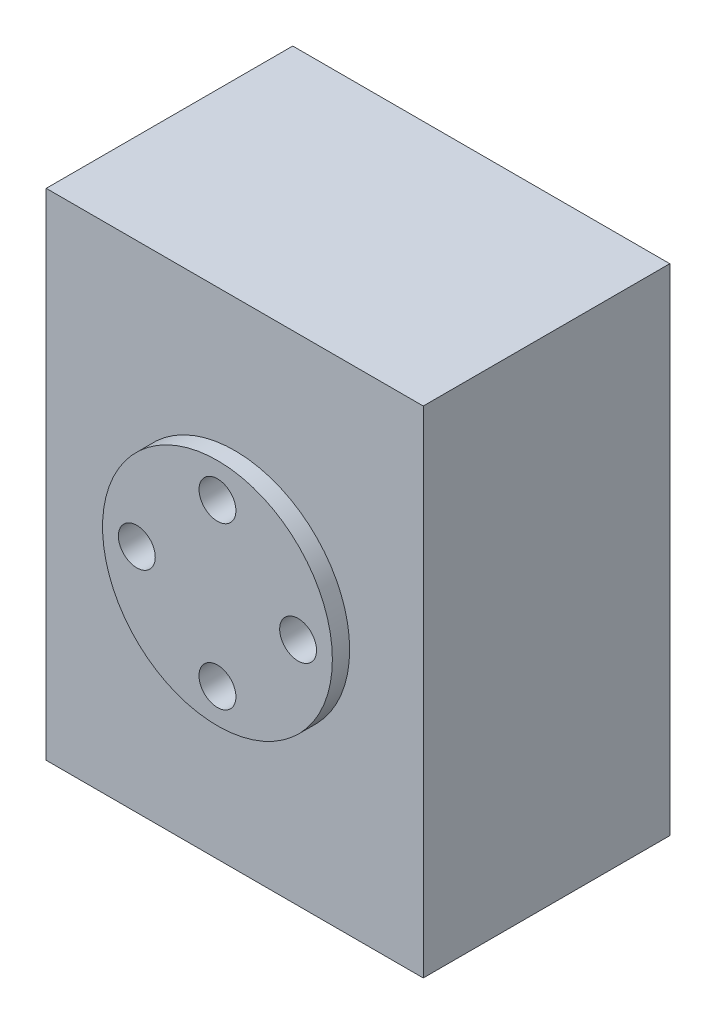
SolidWorks part; units mm, degrees
ref_plane "Front Plane" through (0, 0, 0) normal (0, 0, 1) x (1, 0, 0)
ref_plane "Top Plane" through (0, 0, 0) normal (0, 1, 0) x (1, 0, 0)
ref_plane "Right Plane" through (0, 0, 0) normal (1, 0, 0) x (0, 0, -1)
sketch "Sketch1" plane through (0, 0, 0) normal (0, 0, 1) x (1, 0, 0)
  circle A0 centre (0, 0) radius 9.975
  dimension "D1" = 19.95
extrude "Boss-Extrude1" add sketch "Sketch1" along normal blind 1.5
sketch "Sketch3" plane through (0, 0, 0) normal (0, 0, -1) x (-1, 0, 0)
  line L0 (16.365, 21.5) -> (16.365, -21.5)
  line L1 (-12.365, 17.5) -> (12.365, 17.5)
  line L2 (-12.365, 17.5) -> (-12.365, -17.5)
  line L3 (-12.365, -17.5) -> (12.365, -17.5)
  line L4 (12.365, 17.5) -> (12.365, -17.5)
  line L5 (-12.365, 17.5) -> (12.365, -17.5) construction
  line L6 (-12.365, -17.5) -> (12.365, 17.5) construction
  line L7 (-16.365, -21.5) -> (16.365, -21.5)
  line L8 (-16.365, 21.5) -> (-16.365, -21.5)
  line L9 (-16.365, 21.5) -> (16.365, 21.5)
  point P0 (0, 0)
  dimension "D1" = 35
  dimension "D2" = 24.73
  dimension "D3" = 4
extrude "Boss-Extrude4" add sketch "Sketch3" along normal blind 2.5 contours L2 L1 L4 L3
extrude "Boss-Extrude5" add sketch "Sketch3<5>" along normal blind 21.4
sketch "Sketch3<5>" plane through (0, 0, 0) normal (0, 0, -1) x (-1, 0, 0) same geometry as "Sketch3"
sketch "Sketch4" plane through (0, 0, -2.5) normal (0, 0, -1) x (-1, 0, 0)
  line L1 (12.365, 17.5) -> (7.165, 17.5)
  line L2 (12.365, 17.5) -> (12.365, 16.4)
  line L3 (12.365, 16.4) -> (7.165, 16.4)
  line L4 (7.165, 17.5) -> (7.165, 16.4)
  line L5 (-12.365, 17.5) -> (-7.165, 17.5)
  line L6 (-12.365, 17.5) -> (-12.365, 16.4)
  line L7 (-12.365, 16.4) -> (-7.165, 16.4)
  line L8 (-7.165, 17.5) -> (-7.165, 16.4)
  line L9 (12.365, -17.5) -> (9.165, -17.5)
  line L10 (12.365, -17.5) -> (12.365, -16)
  line L11 (12.365, -16) -> (9.165, -16)
  line L12 (9.165, -17.5) -> (9.165, -16)
  line L13 (-12.365, -17.5) -> (-9.165, -17.5)
  line L14 (-12.365, -17.5) -> (-12.365, -16)
  line L15 (-12.365, -16) -> (-9.165, -16)
  line L16 (-9.165, -17.5) -> (-9.165, -16)
  dimension "D1" = 1.1
  dimension "D2" = 5.2
  dimension "D3" = 5.2
  dimension "D4" = 1.1
  dimension "D5" = 3.2
  dimension "D6" = 1.5
  dimension "D7" = 3.2
extrude "Boss-Extrude6" add sketch "Sketch4" along normal blind 18.9 contours L2 L1 L4 L3 | L6 L5 L8 L7 | L10 L9 L12 L11 | L14 L13 L16 L15
sketch "Sketch6" plane through (0, 0, -2.5) normal (0, 0, -1) x (-1, 0, 0)
  line L1 (9.165, -17.5) -> (-9.165, -17.5)
  line L2 (9.165, -17.5) -> (9.165, -16)
  line L3 (9.165, -16) -> (-9.165, -16)
  line L4 (-9.165, -17.5) -> (-9.165, -16)
extrude "Boss-Extrude7" add sketch "Sketch6" along normal blind 5.3
sketch "Sketch2" plane through (0, 0, 1.5) normal (0, 0, 1) x (1, 0, 0)
  circle A0 centre (0, 0) radius 7 construction
  circle A1 centre (7, 0) radius 1.6
  circle A2 centre (0, -7) radius 1.6
  circle A3 centre (-7, 0) radius 1.6
  circle A4 centre (0, 7) radius 1.6
  point P14 (0, 0)
  dimension "D1" = 14
  dimension "D2" = 3.2
  dimension "D3" = 4
extrude "Cut-Extrude1" cut sketch "Sketch2" against normal blind 37
